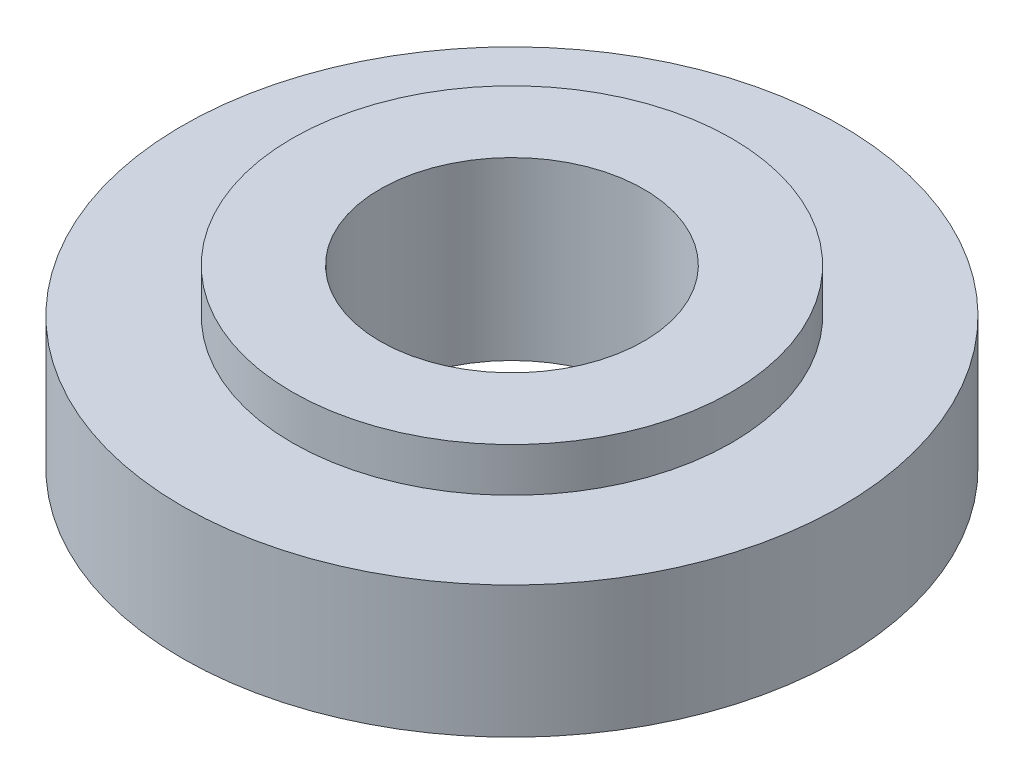
SolidWorks part; units mm, degrees
ref_plane "Front Plane" through (0, 0, 0) normal (0, 0, 1) x (1, 0, 0)
ref_plane "Top Plane" through (0, 0, 0) normal (0, 1, 0) x (1, 0, 0)
ref_plane "Right Plane" through (0, 0, 0) normal (1, 0, 0) x (0, 0, -1)
sketch "Sketch1" plane through (0, 0, 0) normal (0, 1, 0) x (1, 0, 0)
  circle A0 centre (0, 0) radius 3.75
  circle A1 centre (0, 0) radius 2.5
  circle A2 centre (0, 0) radius 1.5
  dimension "D1" = 7.5
  dimension "D2" = 5
  dimension "D3" = 3
extrude "Boss-Extrude1" add sketch "Sketch1" against normal blind 1.5 contours A1 A2 | A0 A1 region at (-3.6439, 0, 0) region at (-2.4293, 0, 0)
extrude "Boss-Extrude2" add sketch "Sketch1<3>" along normal blind 0.5 contours A1 A2 region at (-2.4293, 0, 0)
sketch "Sketch1<3>" plane through (0, 0, 0) normal (0, 1, 0) x (1, 0, 0) same geometry as "Sketch1"
scale "Scale1" scale about centroid uniform scaling yes scale factor 1.667
